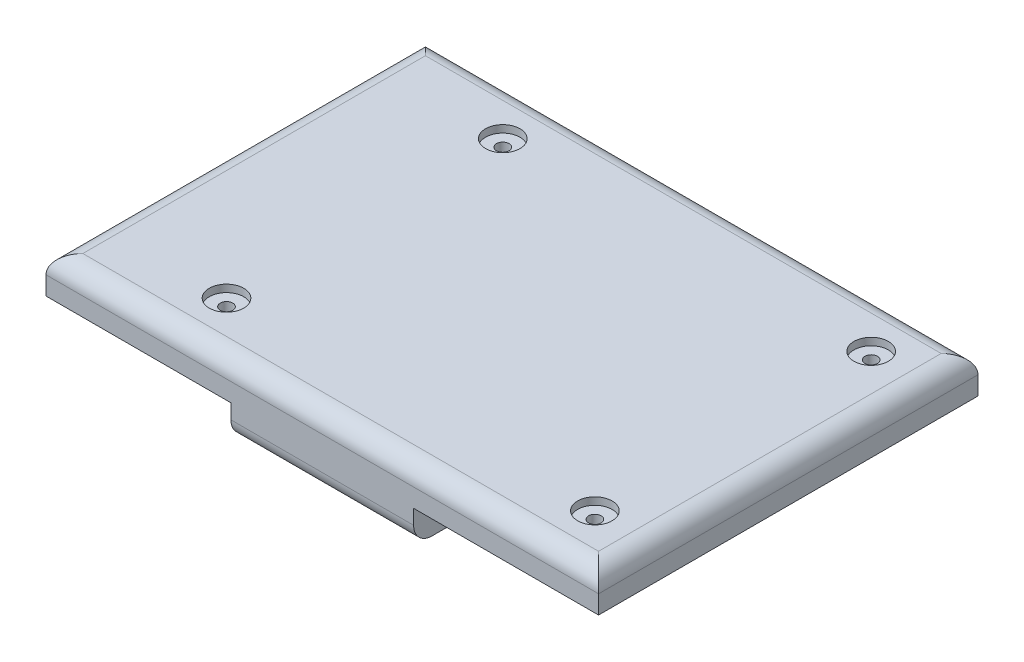
SolidWorks part; units mm, degrees
ref_plane "Front Plane" through (0, 0, 0) normal (0, 0, 1) x (1, 0, 0)
ref_plane "Top Plane" through (0, 0, 0) normal (0, 1, 0) x (1, 0, 0)
ref_plane "Right Plane" through (0, 0, 0) normal (1, 0, 0) x (0, 0, -1)
sketch "Sketch1" plane through (0, 0, 0) normal (0, 1, 0) x (1, 0, 0)
  line L1 (0, 0) -> (150, 0)
  line L2 (0, 0) -> (0, 103)
  line L3 (0, 103) -> (150, 103)
  line L4 (150, 0) -> (150, 103)
  dimension "D1" = 150
  dimension "D2" = 103
extrude "Boss-Extrude1" add sketch "Sketch1" along normal blind 10
sketch "Sketch4" plane through (0, 0, 0) normal (0, -1, 0) x (1, 0, 0)
  line L15 (0, -20) -> (150, -20)
  line L16 (6, -20) -> (144, -20)
  line L18 (150, -83) -> (0, -83)
  line L19 (144, -83) -> (6, -83)
  line L24 (6, -103) -> (6, 0)
  line L25 (6, -83) -> (6, -20)
  line L27 (144, 0) -> (144, -103)
  line L28 (144, -20) -> (144, -83)
  dimension "D1" = 20
  dimension "D2" = 20
  dimension "D3" = 6
  dimension "D4" = 6
sketch "Sketch2" plane through (0, 0, 0) normal (0, -1, 0) x (1, 0, 0)
  line L0 (0, 0) -> (150, 0) construction
  line L1 (50.2, 0) -> (99.8, 0)
  line L2 (50.2, 0) -> (50.2, -13.8)
  line L3 (50.2, -13.8) -> (99.8, -13.8)
  line L4 (99.8, 0) -> (99.8, -13.8)
  line L5 (0, -103) -> (0, 0) construction
  line L6 (150, 0) -> (150, -103) construction
  line L7 (0, -51.5) -> (150, -51.5) construction
  line L8 (99.8, -103) -> (99.8, -89.2)
  line L9 (50.2, -89.2) -> (99.8, -89.2)
  line L10 (50.2, -103) -> (50.2, -89.2)
  line L11 (50.2, -103) -> (99.8, -103)
  dimension "D1" = 50.2
  dimension "D2" = 50.2
  dimension "D3" = 13.8
extrude "Boss-Extrude2" add sketch "Sketch2" along normal blind 9
extrude "Cut-Extrude1" cut sketch "Sketch4" against normal blind 7
fillet "Fillet1" radius 5 8 edges at (75, -9, -89.2) (75, -9, -103) (75, -9, -13.8) (75, -9, 0) (150, 10, -51.5) (75, 10, -103) (75, 10, 0) (0, 10, -51.5)
hole_wizard "CBORE for M3 Hex Head Cap Screw1" positions "Sketch6" profile "Sketch5" counterbore size "M3" standard "ISO" end condition through all
sketch "Sketch6" plane through (0, 10, 0) normal (0, 1, 0) x (1, 0, 0)
  point P0 (35, 89)
  point P3 (35, 14)
  point P6 (135, 14)
  point P9 (135, 89)
sketch "Sketch5" plane through (35, 10, -89) normal (1, 0, 0) x (0, 0, 1)
  line L0 (0, 0) -> (0, 19)
  line L1 (0, 19) -> (1.7, 19)
  line L3 (1.7, 19) -> (1.7, 2)
  line L4 (1.7, 2) -> (4.6755, 2)
  line L5 (4.6755, 2) -> (4.6755, 0)
  line L7 (4.6755, 0) -> (0, 0)
  line L11 (0, -6.35) -> (0, 107.95) construction
  dimension "Thru Hole Dia." = 3.4
  dimension "Thru Hole Depth" = 19
  dimension "C'Bore Dia." = 9.351
  dimension "C'Bore Depth" = 2
